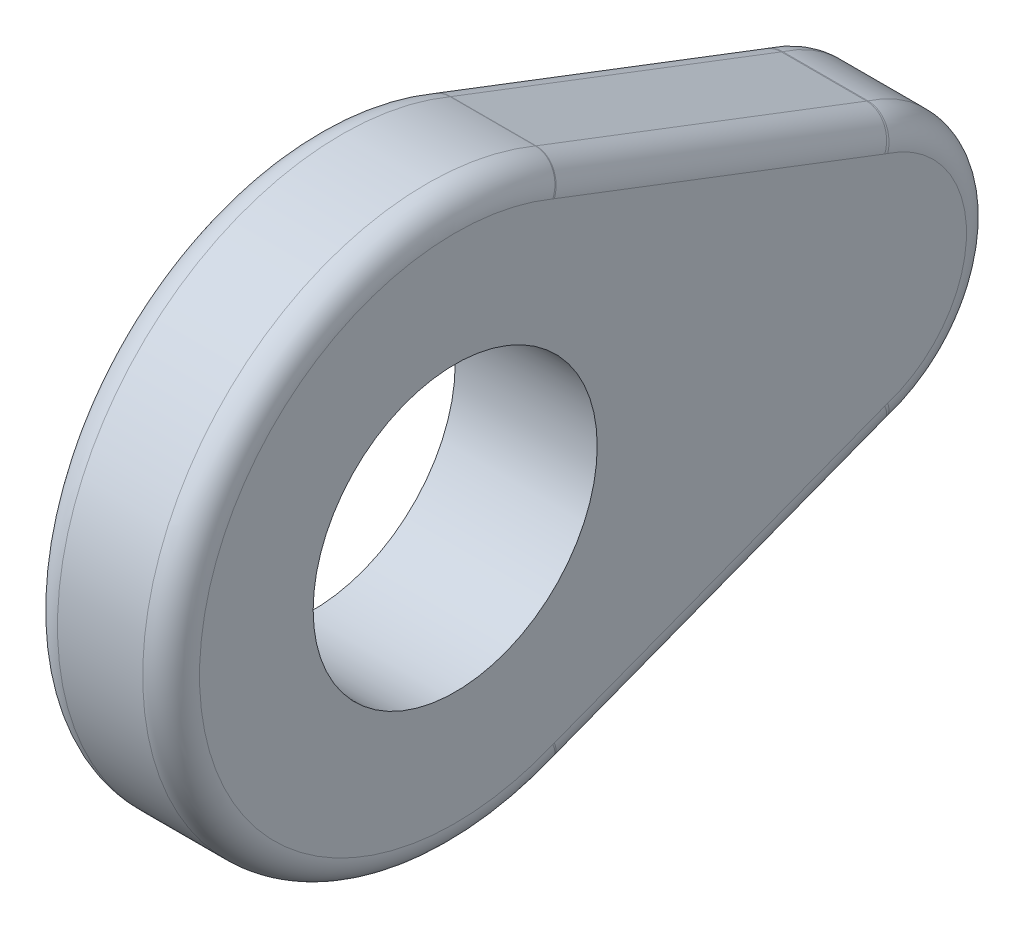
SolidWorks part; units mm, degrees
ref_plane "Front Plane" through (0, 0, 0) normal (0, 0, 1) x (1, 0, 0)
ref_plane "Top Plane" through (0, 0, 0) normal (0, 1, 0) x (1, 0, 0)
ref_plane "Right Plane" through (0, 0, 0) normal (1, 0, 0) x (0, 0, -1)
sketch "Sketch1" plane through (0, 0, 0) normal (1, 0, 0) x (0, 0, -1)
  line L0 (0, 0) -> (19, 0)
  line L1 (0, 0) -> (14, 0)
  line L2 (3.8345, -9.2356) -> (15.5085, -4.767)
  line L3 (3.8345, 9.2356) -> (15.5085, 4.767)
  arc A0 (3.8345, 9.2356) -> (3.8345, -9.2356) centre (0, 0) ccw
  arc A1 (15.5085, -4.767) -> (15.5085, 4.767) centre (14, 0) ccw
  circle A2 centre (0, 0) radius 5
  dimension "D1" = 20
  dimension "D2" = 10
  dimension "D6" = 10
  dimension "D3" = 14
  dimension "D4" = 12.5
  dimension "D5" = 4.767
extrude "Boss-Extrude1" add sketch "Sketch1" along normal blind 5 contours A2 A1 L3 A0 L2 region at (0, -2.7463, -17.7496)
fillet "Fillet2" radius 1 12 edges at (5, -7.0013, -9.6715) (0, -7.0013, -9.6715) (2.5, 9.2356, -3.8345) (5, 0, 10) (2.5, -9.2356, -3.8345) (0, 0, 10) (2.5, -4.767, -15.5085) (5, 0, -19) (2.5, 4.767, -15.5085) (0, 0, -19) (0, 7.0013, -9.6715) (5, 7.0013, -9.6715)
